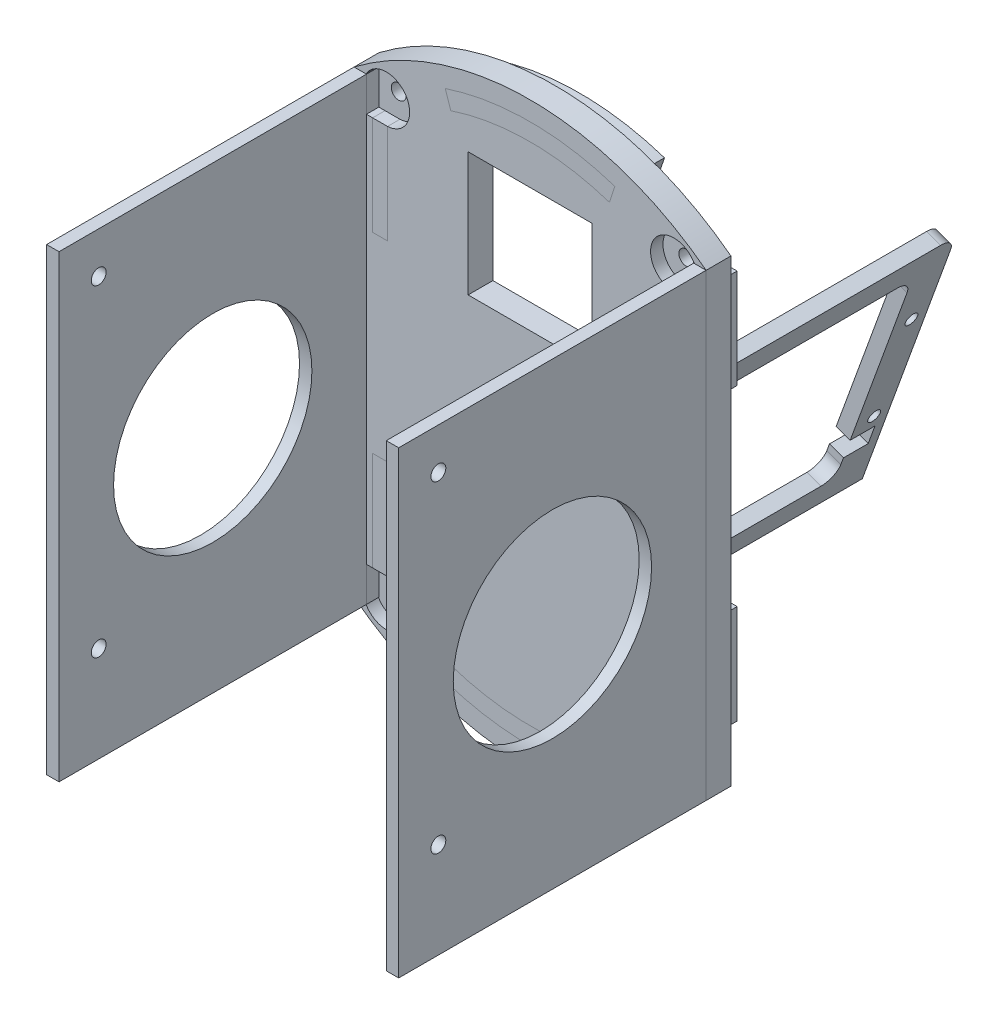
SolidWorks part; units mm, degrees
ref_plane "前视基准面" through (0, 0, 0) normal (0, 0, 1) x (1, 0, 0)
ref_plane "上视基准面" through (0, 0, 0) normal (0, 1, 0) x (1, 0, 0)
ref_plane "右视基准面" through (0, 0, 0) normal (1, 0, 0) x (0, 0, -1)
sketch "草图1" plane through (0, 0, 0) normal (0, 0, 1) x (1, 0, 0)
  line L0 (32, 16.5) -> (32, 39)
  line L2 (35.3725, -46.3006) -> (35.3725, 46.3006)
  line L3 (-35.6275, 46.3006) -> (-35.6275, -46.3006)
  line L6 (32, 39) -> (29, 39)
  line L7 (-29, 39) -> (-32, 39)
  line L8 (32, 39) -> (29, 39)
  line L9 (32, 16.5) -> (32, 39)
  line L10 (30.5, 15) -> (32, 16.5)
  line L11 (30.5, -15) -> (30.5, 15)
  line L12 (32, -16.5) -> (30.5, -15)
  line L13 (32, -39) -> (32, -16.5)
  line L14 (29, -39) -> (32, -39)
  line L15 (-32, -39) -> (-29, -39)
  line L16 (-32, -16.5) -> (-32, -39)
  line L17 (-30.5, -15) -> (-32, -16.5)
  line L18 (-30.5, 15) -> (-30.5, -15)
  line L19 (-32, 16.5) -> (-30.5, 15)
  line L20 (-32, 39) -> (-32, 16.5)
  line L21 (-29, 39) -> (-32, 39)
  arc A0 (26.2317, 48.1637) -> (29, 39) centre (29, 44) ccw
  arc A2 (35.3725, 46.3006) -> (-0.1275, 58.3438) centre (-0.1275, 0) ccw
  arc A3 (-0.1275, 58.3438) -> (-35.6275, 46.3006) centre (-0.1275, 0) ccw
  arc A4 (-35.6275, -46.3006) -> (35.3725, -46.3006) centre (-0.1275, 0) ccw
  arc A5 (-29, 42.5) -> (-29, 45.5) centre (-29, 44) ccw
  arc A9 (-29, 45.5) -> (-29, 42.5) centre (-29, 44) ccw
  arc A10 (-29, 39) -> (-26.2317, 48.1637) centre (-29, 44) ccw
  arc A11 (0, 54.8438) -> (-26.2317, 48.1637) centre (0, 0) ccw
  arc A12 (26.2317, 48.1637) -> (0, 54.8438) centre (0, 0) ccw
  arc A13 (29, 42.5) -> (29, 45.5) centre (29, 44) ccw
  arc A14 (29, 45.5) -> (29, 42.5) centre (29, 44) ccw
  arc A17 (29, -45.5) -> (29, -42.5) centre (29, -44) ccw
  arc A18 (29, -42.5) -> (29, -45.5) centre (29, -44) ccw
  arc A19 (-29, -45.5) -> (-29, -42.5) centre (-29, -44) ccw
  arc A22 (-29, 39) -> (-26.2317, 48.1637) centre (-29, 44) ccw
  arc A23 (0, 54.8438) -> (-26.2317, 48.1637) centre (0, 0) ccw
  arc A24 (26.2317, 48.1637) -> (0, 54.8438) centre (0, 0) ccw
  arc A25 (26.2317, 48.1637) -> (29, 39) centre (29, 44) ccw
  arc A29 (29, -39) -> (26.2317, -48.1637) centre (29, -44) ccw
  arc A30 (-26.2317, -48.1637) -> (26.2317, -48.1637) centre (0, 0) ccw
  arc A31 (-26.2317, -48.1637) -> (-29, -39) centre (-29, -44) ccw
  arc A32 (-29, -42.5) -> (-29, -45.5) centre (-29, -44) ccw
  dimension "D4" = 3.3725
  dimension "D8" = 3.5
  dimension "D1" = 71
  dimension "D2" = 35.5
  dimension "D3" = 92.6013
  dimension "D5" = 3.6275
  dimension "D6" = 7.3006
  dimension "D7" = 22.5
sketch "草图3" plane through (0, 0, 0) normal (0, 0, 1) x (1, 0, 0)
  line L0 (0, 0) -> (0, 46.3) construction
  line L5 (-35.5, -46.3) -> (35.5, -46.3)
  line L6 (-35.5, -46.3) -> (-35.5, 46.3)
  line L7 (-35.5, 46.3) -> (35.5, 46.3)
  line L8 (35.5, -46.3) -> (35.5, 46.3)
  line L9 (-35.5, -46.3) -> (35.5, 46.3) construction
  line L10 (-35.5, 46.3) -> (35.5, -46.3) construction
  line L11 (0, 0) -> (35.5, 0) construction
  line L12 (-31.75, 19.3) -> (-28.75, 19.3)
  line L13 (-31.75, -39.3) -> (31.75, -39.3)
  line L14 (-31.75, -39.3) -> (-31.75, 39.3)
  line L15 (-31.75, 39.3) -> (31.75, 39.3)
  line L16 (31.75, -39.3) -> (31.75, 39.3)
  line L17 (-31.75, -39.3) -> (31.75, 39.3) construction
  line L18 (-31.75, 39.3) -> (31.75, -39.3) construction
  line L19 (31.75, 39.3) -> (28.75, 39.3)
  line L20 (31.75, 39.3) -> (31.75, 19.3)
  line L21 (31.75, 19.3) -> (28.75, 19.3)
  line L22 (28.75, 39.3) -> (28.75, 19.3)
  line L23 (-28.75, 39.3) -> (-28.75, 19.3)
  line L24 (-31.75, 39.3) -> (-28.75, 39.3)
  line L25 (-31.75, 39.3) -> (-31.75, 19.3)
  line L26 (31.75, -19.3) -> (28.75, -19.3)
  line L27 (28.75, -39.3) -> (28.75, -19.3)
  line L28 (31.75, -39.3) -> (28.75, -39.3)
  line L29 (31.75, -39.3) -> (31.75, -19.3)
  line L30 (-31.75, -39.3) -> (-28.75, -39.3)
  line L31 (-28.75, -39.3) -> (-28.75, -19.3)
  line L32 (-31.75, -19.3) -> (-28.75, -19.3)
  line L33 (-31.75, -39.3) -> (-31.75, -19.3)
  line L34 (-16, 48.4252) -> (-17.098, 51.7485)
  line L35 (16, 48.4252) -> (17.098, 51.7485)
  line L36 (16, -48.4252) -> (17.098, -51.7485)
  line L37 (-16, -48.4252) -> (-17.098, -51.7485)
  line L38 (-35.5, -46.3) -> (-33, -46.3)
  line L39 (-12.5, 18) -> (12.5, 18)
  line L40 (-12.5, 18) -> (-12.5, 43)
  line L41 (-12.5, 43) -> (12.5, 43)
  line L42 (12.5, 18) -> (12.5, 43)
  line L43 (-12.5, 18) -> (12.5, 43) construction
  line L44 (-12.5, 43) -> (12.5, 18) construction
  line L49 (31.75, 39.3) -> (33, 39.3)
  line L50 (-0.8151, -38.3285) -> (2.004, -39.3546)
  line L55 (35.5, 46.3) -> (33, 46.3)
  line L56 (35.5, 46.3) -> (35.5, -46.3)
  line L57 (35.5, -46.3) -> (33, -46.3)
  line L58 (33, 46.3) -> (33, -46.3)
  line L59 (-33, 46.3) -> (-33, -46.3)
  line L60 (-35.5, 46.3) -> (-33, 46.3)
  line L61 (-35.5, 46.3) -> (-35.5, -46.3)
  line L62 (-0.8151, -38.3285) -> (17.996, 13.3546)
  line L63 (17.996, 13.3546) -> (20.8151, 12.3285)
  line L64 (2.004, -39.3546) -> (20.8151, 12.3285)
  line L65 (-0.8151, -38.3285) -> (20.8151, 12.3285) construction
  line L66 (17.996, 13.3546) -> (2.004, -39.3546) construction
  line L67 (31.75, -39.3) -> (33, -39.3)
  line L68 (-31.75, -39.3) -> (-33, -39.3)
  line L69 (-31.75, 39.3) -> (-33, 39.3)
  line L70 (0, 9) -> (0, 7) construction
  line L71 (2, 9) -> (2, 7)
  line L72 (-2, 9) -> (-2, 7)
  line L73 (0, -20.5) -> (0, 2.5) construction
  line L74 (-1.5, -20.5) -> (-1.5, 2.5)
  line L75 (1.5, -20.5) -> (1.5, 2.5)
  line L76 (0, -20.5) -> (0, -26) construction
  line L77 (0, -26) -> (0, -39.3) construction
  line L78 (0, -31.5) -> (0, -41.5) construction
  line L79 (1.5, -31.5) -> (1.5, -41.5)
  line L80 (-1.5, -31.5) -> (-1.5, -41.5)
  arc A2 (-35.5, 46.3) -> (35.5, 46.3) centre (0, 0) cw
  arc A3 (-35.5, -46.3) -> (35.5, -46.3) centre (0, 0) ccw
  circle A4 centre (-29, 44) radius 1.5
  circle A5 centre (29, 44) radius 1.5
  circle A6 centre (29, -44) radius 1.5
  circle A7 centre (-29, -44) radius 1.5
  arc A9 (28.75, 39.3) -> (26.2047, 47.7867) centre (29, 44) cw
  arc A10 (-28.75, 39.3) -> (-26.2047, 47.7867) centre (-29, 44) ccw
  arc A11 (-28.75, -39.3) -> (-26.2047, -47.7867) centre (-29, -44) cw
  arc A12 (28.75, -39.3) -> (26.2047, -47.7867) centre (29, -44) ccw
  arc A13 (-26.2047, -47.7867) -> (26.2047, -47.7867) centre (0, 0) ccw
  arc A14 (26.2047, 47.7867) -> (-26.2047, 47.7867) centre (0, 0) ccw
  arc A15 (-16, 48.4252) -> (16, 48.4252) centre (0, 0) cw
  arc A16 (-16, -48.4252) -> (16, -48.4252) centre (0, 0) ccw
  arc A17 (26.2047, 47.7867) -> (33.1064, 46.3) centre (29, 44) cw
  arc A18 (2, 9) -> (-2, 9) centre (0, 9) ccw
  arc A19 (26.2047, -47.7867) -> (33.1064, -46.3) centre (29, -44) ccw
  arc A20 (-26.2047, -47.7867) -> (-33.1064, -46.3) centre (-29, -44) cw
  arc A21 (-26.2047, 47.7867) -> (-33.1064, 46.3) centre (-29, 44) ccw
  arc A22 (-2, 7) -> (2, 7) centre (0, 7) ccw
  arc A23 (-1.5, -20.5) -> (1.5, -20.5) centre (0, -20.5) ccw
  arc A24 (1.5, 2.5) -> (-1.5, 2.5) centre (0, 2.5) ccw
  circle A25 centre (0, -26) radius 2
  arc A26 (1.5, -31.5) -> (-1.5, -31.5) centre (0, -31.5) ccw
  arc A27 (-1.5, -41.5) -> (1.5, -41.5) centre (0, -41.5) ccw
  point P0 (0, 0)
  point P47 (0, 30.5)
  point P52 (10, -13)
  point P65 (0, 8)
  point P78 (0, -9)
  point P89 (0, -36.5)
  dimension "D1" = 71
  dimension "D3" = 58
  dimension "D4" = 88
  dimension "D5" = 3
  dimension "D10" = 54.5
  dimension "D11" = 54.5
  dimension "D12" = 51
  dimension "D22" = 70
  dimension "D23" = 2
  dimension "D27" = 1.5
  dimension "D28" = 5.5
  dimension "D29" = 4
  dimension "D31" = 1.5
  dimension "D2" = 92.6
  dimension "D6" = 3.75
  dimension "D7" = 7
  dimension "D8" = 3
  dimension "D9" = 20
  dimension "D13" = 32
  dimension "D14" = 25
  dimension "D15" = 25
  dimension "D16" = 62
  dimension "D17" = 3
  dimension "D18" = 55
  dimension "D19" = 10
  dimension "D20" = 2.5
  dimension "D21" = 13
  dimension "D24" = 2
  dimension "D25" = 21.5
  dimension "D26" = 23
  dimension "D30" = 5.5
  dimension "D32" = 10
  dimension "D33" = 5.5
extrude "凸台-拉伸4" add sketch "草图3<6>" against normal blind 5 contours A21 A14 A17 L55 A2 L7 | L59 L60 L7 L6 L5 L38 | L15 A10 L7 L59 L69 A4 | A10 A21 L60 L7 | A15 L34 A14 A10 L7 A9 L35 | A10 L15 L40 L41 L42 A9 L7 | A9 L15 L49 L58 L7 A5 | A17 A9 L7 | L7 L58 L5 L57 L8 L55 | L16 L67 L58 L49 | L14 L69 L59 L68 | A12 L13 A11 L5 | A11 L13 L68 L59 L5 A7 | A20 A11 L5 L38 | L37 A16 L36 A13 A12 L5 A11 | A13 A20 L5 A3 L57 A19 | A12 A19 L5 | L13 A12 L5 L58 L67 A6 | A26 L79 L62 L63 L64 L13 L27 L26 L16 L21 L22 L15 L42 L39 L40 L23 L12 L14 L32 L31 L80 A25 A24 L75 A23 L74 A22 L72 A18 L71 | L72 A22 L71 A18 | L75 A24 L74 A23 | A25 | L80 A27 L79 L13 | L79 L62 L50 | L79 A26 L80 L13 L50 L62 region at (-34.25, 0, 0) region at (-34.3032, -47.0201, 0) region at (-29, -47.2875, 0) region at (0, 57.6232, 0) region at (34.25, 0, 0) region at (-32.8883, -42.8, 0) region at (0, -48.3169, 0) region at (-29, 47.2875, 0) region at (29, -47.2875, 0) region at (-24.3702, -41.4494, 0) region at (-32.375, 0, 0) region at (-28.9468, 46.1883, 0) region at (0, 48.3169, 0) region at (29, 47.2875, 0) region at (28.9468, -46.1883, 0) region at (-27.7395, -29.3, 0) region at (0, 43.3122, 0) region at (32.8883, 42.8, 0) region at (32.375, 0, 0) region at (-0.3266, -34.0494, 0) region at (0, -41.0056, 0) region at (0.7283, -36.4892, 0) region at (0, 8, 0) region at (0, -9, 0) region at (0, -26, 0)
sketch "草图3<6>" plane through (0, 0, 0) normal (0, 0, 1) x (1, 0, 0) same geometry as "草图3"
extrude "凸台-拉伸7" add sketch "草图3<9>" against normal blind 65 contours L50 L64 L63 L42 L62 | L50 L64 L13 | L50 L79 L13 | L79 L62 L50 region at (1.9606, -39.3182, 0) region at (10.4937, -11.749, 0) region at (1.618, -39.257, 0) region at (0.7283, -36.4892, 0)
sketch "草图3<9>" plane through (0, 0, 0) normal (0, 0, 1) x (1, 0, 0) same geometry as "草图3"
extrude "凸台-拉伸6" add sketch "草图3<8>" along normal blind 62 separate body contours L59 L7 L6 L5 | L7 L58 L5 L8 region at (-34.25, 0, 0) region at (34.25, 0, 0)
sketch "草图3<8>" plane through (0, 0, 0) normal (0, 0, 1) x (1, 0, 0) same geometry as "草图3"
sketch "草图4" plane through (14.4179, -5.2477, 0) normal (0.9397, -0.342, 0) x (0, 0, -1)
  line L0 (13, -9) -> (58, -9) construction
  line L1 (5, -36.2958) -> (5, 18.7042) construction
  line L2 (58, -23) -> (63, -23)
  line L3 (58, -23) -> (58, -27)
  line L4 (58, -27) -> (63, -27)
  line L5 (0, -47.7891) -> (0, 47.7891) construction
  line L6 (63, -23) -> (63, -27)
  line L7 (58, -31.5) -> (13, -31.5)
  line L8 (58, -31.5) -> (58, 13.5)
  line L9 (58, 13.5) -> (13, 13.5)
  line L10 (13, -31.5) -> (13, 13.5)
  line L11 (58, -31.5) -> (13, 13.5) construction
  line L12 (58, 13.5) -> (13, -31.5) construction
  line L17 (15, -24) -> (5, -24)
  line L18 (15, -24) -> (15, -16)
  line L19 (15, -16) -> (5, -16)
  line L20 (5, -24) -> (5, -16)
  line L21 (15, -24) -> (5, -16) construction
  line L22 (15, -16) -> (5, -24) construction
  line L24 (15, -2) -> (5, -2)
  line L25 (15, -2) -> (15, 6)
  line L26 (15, 6) -> (5, 6)
  line L27 (5, -2) -> (5, 6)
  line L28 (15, -2) -> (5, 6) construction
  line L29 (15, 6) -> (5, -2) construction
  circle A0 centre (10, -20) radius 1.25
  circle A1 centre (10, 2) radius 1.25
  circle A2 centre (61.8, -20) radius 1.25
  circle A3 centre (61.8, 2) radius 1.25
  point P14 (35.5, -9)
  dimension "D2" = 10
  dimension "D3" = 2.5
  dimension "D5" = 51.8
  dimension "D8" = 3
  dimension "D14" = 8
  dimension "D6" = 45
  dimension "D7" = 45
  dimension "D9" = 5
  dimension "D10" = 4
  dimension "D11" = 3
  dimension "D12" = 9
  dimension "D13" = 11
  dimension "D15" = 8
  dimension "D4" = 2
extrude "切除-拉伸2" cut sketch "草图4" against normal up to next (3 mm away) contours L10 L7 L8 L3 L9 | L6 L2 L3 L4 | A1 | A0 | L18 L19 L10 L17 | L25 L26 L10 L24 | A2 | A3 region at (5.8674, -28.74, -60.5) region at (11.3397, -13.7049, -35.8452) region at (15.1019, -3.3683, -14) region at (7.5775, -24.0415, -14) region at (7.5775, -24.0415, -10) region at (15.1019, -3.3683, -10)
sketch "草图7" plane through (0, 0, 0) normal (1, 0, 0) x (0, 0, -1)
  line L0 (-62, -46.3) -> (0, 46.3) construction
  line L1 (0, -46.3) -> (-62, 46.3) construction
  line L2 (-62, -46.3) -> (-83.5006, -46.3)
  line L3 (-62, 46.3) -> (-83.5006, 46.3)
  line L4 (0, -46.3) -> (0, 46.3)
  line L5 (0, 46.3) -> (-62, 46.3)
  line L6 (-62, 46.3) -> (-62, -46.3)
  line L7 (-62, -46.3) -> (0, -46.3)
  line L8 (0, -46.3) -> (0, 46.3)
  line L9 (0, 46.3) -> (-62, 46.3)
  line L10 (-62, 46.3) -> (-62, -46.3)
  line L11 (-62, -46.3) -> (0, -46.3)
  line L12 (-31, -46.3) -> (-31, 46.3) construction
  line L13 (-62, -46.3) -> (-62, -62.7615)
  line L14 (-62, 62.7615) -> (-62, 46.3)
  circle A0 centre (-8, 38) radius 1.5
  circle A2 centre (-8, -27) radius 1.5
  circle A3 centre (-54, 38) radius 1.5
  circle A4 centre (-54, -27) radius 1.5
  circle A5 centre (-31, 0) radius 20
  arc A6 (-62, 62.7615) -> (-62, -62.7615) centre (-31, 0) ccw
  arc A7 (-62, 58.2382) -> (-62, -58.2382) centre (-31, 0) ccw
  point P0 (0, 30.5)
  point P16 (-78, -46.3)
  dimension "D1" = 3
  dimension "D4" = 3
  dimension "D6" = 8
  dimension "D8" = 46
  dimension "D10" = 40
  dimension "D11" = 140
  dimension "D2" = 7.5
  dimension "D3" = 8
  dimension "D5" = 65
  dimension "D12" = 47
  dimension "D9" = 0
  dimension "D7" = 2
extrude "切除-拉伸3" cut sketch "草图7" against normal through all both and the other way through all contours A5 | A3 | A4 region at (0, 38, 54) region at (0, -27, 54) region at (0, 0, 31)
sketch "草图8" plane through (0, 0, 62) normal (0, 0, 1) x (1, 0, 0)
  line L0 (35.5, 46.3) -> (33, 46.3) construction
  line L1 (33, 46.3) -> (33, -46.3) construction
  line L2 (33, -46.3) -> (35.5, -46.3) construction
  line L3 (35.5, -46.3) -> (35.5, 46.3) construction
  line L4 (-33, -46.3) -> (-33, 46.3) construction
  line L5 (-33, 46.3) -> (-35.5, 46.3) construction
  line L6 (-35.5, 46.3) -> (-35.5, -46.3) construction
  line L7 (-35.5, -46.3) -> (-33, -46.3) construction
  line L8 (35.5, 46.3) -> (33, 46.3)
  line L9 (33, 46.3) -> (33, -46.3)
  line L10 (33, -46.3) -> (35.5, -46.3)
  line L11 (35.5, -46.3) -> (35.5, 46.3)
  line L12 (-33, -46.3) -> (-33, 46.3)
  line L13 (-33, 46.3) -> (-35.5, 46.3)
  line L14 (-35.5, 46.3) -> (-35.5, -46.3)
  line L15 (-35.5, -46.3) -> (-33, -46.3)
extrude "切除-拉伸4" cut sketch "草图3" against normal blind 2.5 contours L15 A10 L7 L59 L69 A4 | A10 A21 L60 L7 | A9 L15 L49 L58 L7 A5 | A17 A9 L7 | L13 A12 L5 L58 L67 A6 | A12 A19 L5 | A11 L13 L68 L59 L5 A7 | A20 A11 L5 L38 region at (-29, -47.2875, 0) region at (-32.8883, -42.8, 0) region at (-29, 47.2875, 0) region at (29, -47.2875, 0) region at (-28.9468, 46.1883, 0) region at (29, 47.2875, 0) region at (28.9468, -46.1883, 0) region at (32.8883, 42.8, 0)
extrude "凸台-拉伸8" add sketch "草图3<12>" against normal blind 10 separate body contours L23 L15 L14 L12 | L34 A15 L35 A14 | L15 L22 L21 L16 | L27 L13 L16 L26 | L32 L14 L13 L31 | A16 L37 A13 L36 region at (0, -51.8783, 0) region at (-30.25, -29.3, 0) region at (0, 51.8783, 0) region at (30.25, -29.3, 0) region at (-30.25, 29.3, 0) region at (30.25, 29.3, 0)
sketch "草图3<12>" plane through (0, 0, 0) normal (0, 0, 1) x (1, 0, 0) same geometry as "草图3"
fillet "圆角1" radius 3 6 edges at (2.2347, -34.335, -58) (17.6256, 7.9512, -58) (2.2347, -34.335, -13) (17.6256, 7.9512, -13) (19.4056, 12.8415, -65) (0.3425, -38.7498, -65)
fillet "圆角5" radius 5 1 edges at (11.4095, -13.513, -5)
extrude "切除-拉伸5" cut sketch "草图4<4>" along normal blind 10 contours L17 L20 L19 L18 | L24 L27 L26 L25
sketch "草图4<4>" plane through (14.4179, -5.2477, 0) normal (0.9397, -0.342, 0) x (0, 0, -1) same geometry as "草图4"
